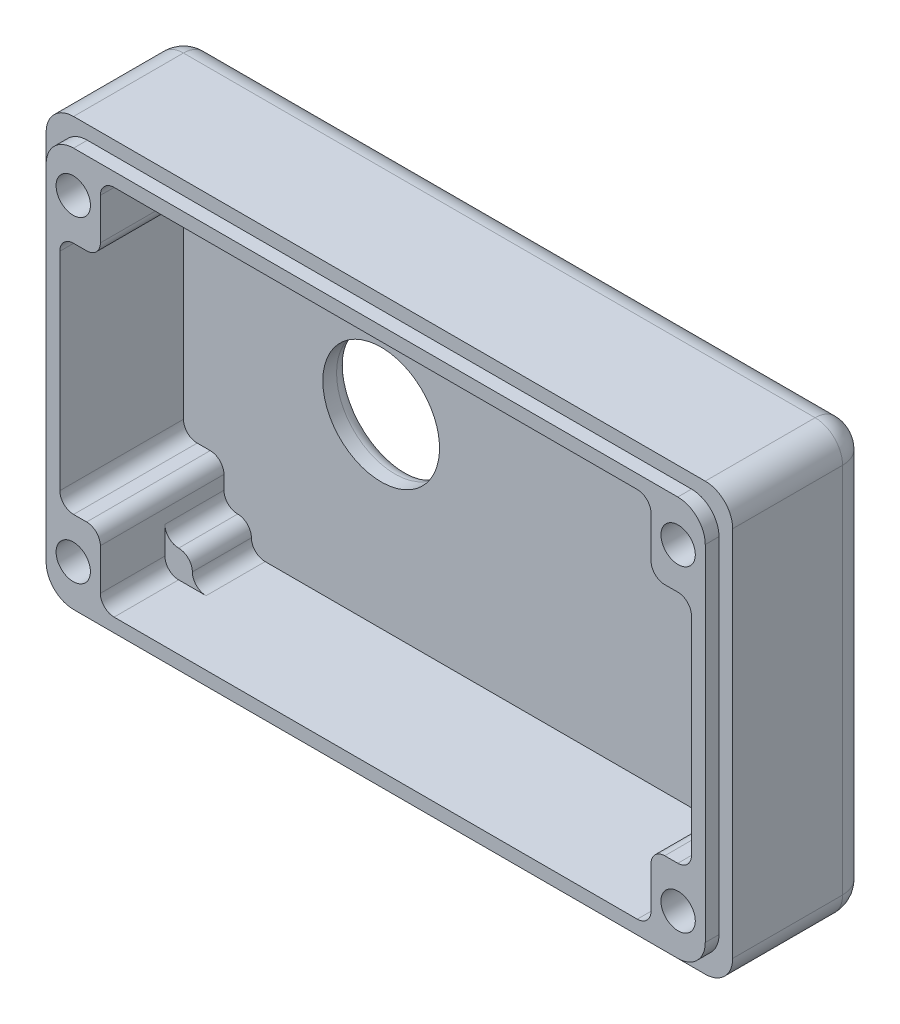
SolidWorks part; units mm, degrees
material "ABS"
ref_plane "Front" through (0, 0, 0) normal (0, 0, 1) x (1, 0, 0)
ref_plane "Top" through (0, 0, 0) normal (0, 1, 0) x (1, 0, 0)
ref_plane "Right" through (0, 0, 0) normal (1, 0, 0) x (0, 0, -1)
sketch "Sketch1" plane through (0, 0, 0) normal (0, 0, 1) x (1, 0, 0)
  line L1 (-25, -15.55) -> (25, -15.55)
  line L2 (-25, -15.55) -> (-25, 15.55)
  line L3 (-25, 15.55) -> (25, 15.55)
  line L4 (25, -15.55) -> (25, 15.55)
  line L5 (-25, -15.55) -> (25, 15.55) construction
  line L6 (-25, 15.55) -> (25, -15.55) construction
  point P0 (0, 0)
  dimension "D1" = 50
  dimension "D2" = 31.1
extrude "Boss-Extrude1" add sketch "Sketch1" along normal blind 11
sketch "Sketch2" plane through (0, 0, 11) normal (0, 0, 1) x (1, 0, 0)
  line L0 (-25, 15.55) -> (-25, -15.55) construction
  line L1 (-23, -13.55) -> (23, -13.55)
  line L2 (-23, -13.55) -> (-23, 13.55)
  line L3 (-23, 13.55) -> (23, 13.55)
  line L4 (23, -13.55) -> (23, 13.55)
  line L5 (-23, -13.55) -> (23, 13.55) construction
  line L6 (-23, 13.55) -> (23, -13.55) construction
  line L7 (25, 15.55) -> (-25, 15.55) construction
  point P0 (0, 0)
  dimension "D1" = 2
  dimension "D2" = 2
extrude "Cut-Extrude1" cut sketch "Sketch2" against normal offset from surface (9 mm away) 2 up to face at (0, 0, 0)
sketch "Sketch3" plane through (0, 0, 0) normal (0, 0, -1) x (-1, 0, 0)
  line L0 (25, 15.55) -> (25, -15.55) construction
  line L1 (12.85, 4.2) -> (4.35, 4.2) construction
  line L2 (12.85, 4.2) -> (12.85, -4.3) construction
  line L3 (12.85, -4.3) -> (4.35, -4.3) construction
  line L4 (4.35, 4.2) -> (4.35, -4.3) construction
  line L5 (12.85, 4.2) -> (4.35, -4.3) construction
  line L6 (12.85, -4.3) -> (4.35, 4.2) construction
  line L7 (25, -15.55) -> (-25, -15.55) construction
  circle A0 centre (8.6, -0.05) radius 4.25
  point P0 (8.6, -0.05)
  dimension "D1" = 8.5
  dimension "D5" = 8.5
  dimension "D2" = 16.4
  dimension "D3" = 15.5
  dimension "D4" = 8.5
extrude "Cut-Extrude2" cut sketch "Sketch3" against normal up to surface (2 mm away) up to face at (0, 0, 2)
fillet "Fillet1" radius 1 1 edges at (-12.85, -0.05, 0)
sketch "Sketch4" plane through (0, 0, 11) normal (0, 0, 1) x (1, 0, 0)
  line L5 (-25, 15.55) -> (-25, -15.55) construction
  line L6 (-25, -15.55) -> (25, -15.55)
  line L7 (-24, -14.55) -> (24, -14.55)
  line L8 (-24, -14.55) -> (-24, 14.55)
  line L9 (-24, 14.55) -> (24, 14.55)
  line L10 (24, -14.55) -> (24, 14.55)
  line L11 (-24, -14.55) -> (24, 14.55) construction
  line L12 (-24, 14.55) -> (24, -14.55) construction
  line L13 (-25, -15.55) -> (-25, 15.55)
  line L14 (-25, 15.55) -> (25, 15.55)
  line L15 (25, -15.55) -> (25, 15.55)
  line L16 (-25, -15.55) -> (25, 15.55) construction
  line L17 (-25, 15.55) -> (25, -15.55) construction
  point P0 (0, 0)
  point P1 (0, 0)
  point P5 (0, 0)
  dimension "D1" = 1
  dimension "D2" = 1
extrude "Cut-Extrude3" cut sketch "Sketch4" against normal blind 1
sketch "Sketch5" plane through (0, 0, 2) normal (0, 0, 1) x (1, 0, 0)
  line L0 (-23, 0) -> (23, 0) construction
  line L1 (-23, 13.55) -> (-20.05, 13.55)
  line L2 (-23, 13.55) -> (-23, 8.55)
  line L3 (-23, 8.55) -> (-20.05, 8.55)
  line L4 (-20.05, 13.55) -> (-20.05, 8.55)
  line L5 (-23, 13.55) -> (-23, -13.55) construction
  line L7 (0, 13.55) -> (0, -13.55) construction
  line L8 (23, 13.55) -> (-23, 13.55) construction
  line L10 (23, 8.55) -> (20.05, 8.55)
  line L11 (20.05, 13.55) -> (20.05, 8.55)
  line L12 (23, 13.55) -> (20.05, 13.55)
  line L13 (23, 13.55) -> (23, 8.55)
  line L14 (-23, -8.55) -> (-20.05, -8.55)
  line L15 (-20.05, -13.55) -> (-20.05, -8.55)
  line L16 (-23, -13.55) -> (-20.05, -13.55)
  line L17 (-23, -13.55) -> (-23, -8.55)
  line L18 (23, -13.55) -> (23, -8.55)
  line L19 (23, -13.55) -> (20.05, -13.55)
  line L20 (20.05, -13.55) -> (20.05, -8.55)
  line L21 (23, -8.55) -> (20.05, -8.55)
  line L22 (23, -13.55) -> (23, 13.55) construction
  line L23 (-23, -13.55) -> (23, -13.55) construction
  dimension "D1" = 2.95
  dimension "D2" = 5
extrude "Boss-Extrude2" add sketch "Sketch5" along normal up to surface (9 mm away) up to face at (0, 0, 11)
sketch "Sketch6" plane through (0, 0, 11) normal (0, 0, 1) x (1, 0, 0)
  line L0 (0, 15.55) -> (0, -15.55) construction
  line L1 (25, 15.55) -> (-25, 15.55) construction
  line L2 (-25, -15.55) -> (25, -15.55) construction
  line L3 (-25, 0) -> (25, 0) construction
  line L6 (-25, 15.55) -> (-25, -15.55) construction
  line L7 (25, -15.55) -> (25, 15.55) construction
  line L8 (-24, 14.55) -> (-20.05, 8.55) construction
  line L9 (-20.05, 14.55) -> (-24, 8.55) construction
  line L10 (24, 14.55) -> (-24, 14.55) construction
  line L11 (-24, 14.55) -> (-24, -14.55) construction
  line L13 (-20.05, 14.55) -> (-20.05, 13.55) construction
  line L14 (-24, 8.55) -> (-23, 8.55) construction
  circle A0 centre (-22.025, 11.55) radius 1.25
  circle A1 centre (22.025, 11.55) radius 1.25
  circle A2 centre (-22.025, -11.55) radius 1.25
  circle A3 centre (22.025, -11.55) radius 1.25
  dimension "D1" = 2.5
extrude "Cut-Extrude4" cut sketch "Sketch6" against normal blind 8
fillet "Fillet2" radius 2 12 edges at (25, 0, 0) (0, -15.55, 0) (-25, 0, 0) (0, 15.55, 0) (24, 14.55, 10.5) (-24, 14.55, 10.5) (-24, -14.55, 10.5) (24, -14.55, 10.5) (25, -15.55, 5) (25, 15.55, 5) (-25, -15.55, 5) (-25, 15.55, 5)
sketch "Sketch7" plane through (0, 0, 2) normal (0, 0, 1) x (1, 0, 0)
  line L0 (-25, 0) -> (25, 0) construction
  line L1 (-20.05, 13.55) -> (-18.05, 13.55)
  line L2 (-20.05, 13.55) -> (-20.05, 11.55)
  line L3 (-20.05, 11.55) -> (-18.05, 11.55)
  line L4 (-18.05, 13.55) -> (-18.05, 11.55)
  line L5 (-25, 13.55) -> (-25, -13.55) construction
  line L6 (25, -13.55) -> (25, 13.55) construction
  line L7 (0, 15.55) -> (0, -15.55) construction
  line L8 (23, 15.55) -> (-23, 15.55) construction
  line L9 (-23, -15.55) -> (23, -15.55) construction
  line L10 (20.05, 11.55) -> (18.05, 11.55)
  line L11 (18.05, 13.55) -> (18.05, 11.55)
  line L12 (20.05, 13.55) -> (18.05, 13.55)
  line L13 (20.05, 13.55) -> (20.05, 11.55)
  line L14 (20.05, -13.55) -> (20.05, -11.55)
  line L15 (20.05, -13.55) -> (18.05, -13.55)
  line L16 (18.05, -13.55) -> (18.05, -11.55)
  line L17 (20.05, -11.55) -> (18.05, -11.55)
  line L18 (-20.05, -11.55) -> (-18.05, -11.55)
  line L19 (-18.05, -13.55) -> (-18.05, -11.55)
  line L20 (-20.05, -13.55) -> (-18.05, -13.55)
  line L21 (-20.05, -13.55) -> (-20.05, -11.55)
  dimension "D1" = 2
  dimension "D2" = 2
extrude "Boss-Extrude3" add sketch "Sketch7" along normal blind 4.3
fillet "Fillet3" radius 1 24 edges at (23, 8.55, 6.5) (20.05, 8.55, 6.5) (20.05, 13.55, 8.65) (-20.05, 13.55, 8.65) (-23, 8.55, 6.5) (-23, -8.55, 6.5) (-20.05, -8.55, 6.5) (-20.05, -13.55, 8.65) (20.05, -13.55, 8.65) (20.05, -8.55, 6.5) (23, -8.55, 6.5) (-20.05, 8.55, 6.5) (-18.05, -11.55, 4.15) (-20.05, -11.55, 4.15) (-18.05, 11.55, 4.15) (-18.05, 13.55, 4.15) (18.05, 13.55, 4.15) (18.05, 11.55, 4.15) (20.05, 11.55, 4.15) (20.05, -11.55, 4.15) (18.05, -11.55, 4.15) (18.05, -13.55, 4.15) (-18.05, -13.55, 4.15) (-20.05, 11.55, 4.15)
